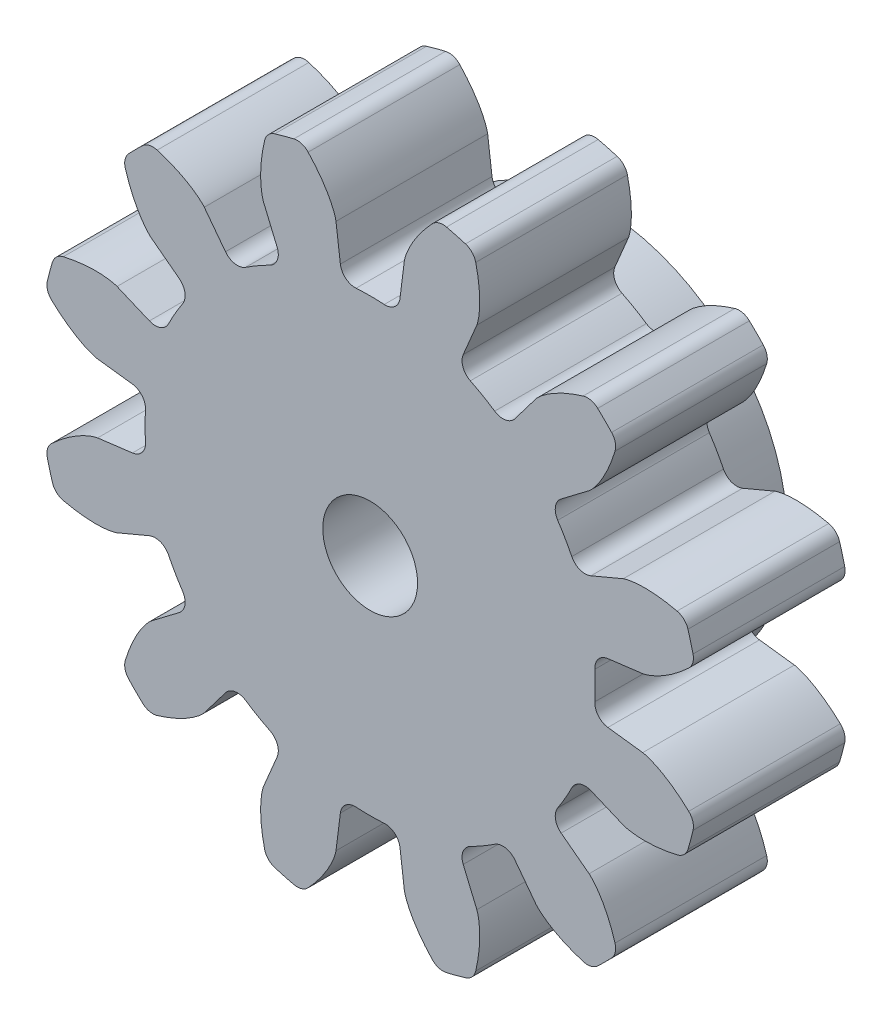
SolidWorks part; units mm, degrees
material "Brass"
ref_plane "Front Plane" through (0, 0, 0) normal (0, 0, 1) x (1, 0, 0)
ref_plane "Top Plane" through (0, 0, 0) normal (0, 1, 0) x (1, 0, 0)
ref_plane "Right Plane" through (0, 0, 0) normal (1, 0, 0) x (0, 0, -1)
sketch "Sketch1" plane through (0, 0, 0) normal (0, 0, 1) x (1, 0, 0)
  circle A0 centre (0, 0) radius 8.75
  dimension "D1" = 17.5
extrude "Boss-Extrude1" add sketch "Sketch1" along normal blind 4
sketch "Sketch2" plane through (0, 0, 4) normal (0, 0, 1) x (1, 0, 0)
  line L0 (7.1881, 0.9014) -> (0, 0) construction
  line L1 (0, 0) -> (7.1881, -0.9014) construction
  line L2 (5.8914, 0.7388) -> (7.1881, 0.9014)
  line L3 (5.8914, -0.7388) -> (7.1881, -0.9014)
  circle A0 centre (0, 0) radius 8.75 construction
  circle A1 centre (0, 0) radius 7.2444 construction
  circle A2 centre (0, 0) radius 7.5 construction
  circle A3 centre (0, 0) radius 5.9375 construction
  arc A4 (8.5637, 1.7962) -> (8.5637, -1.7962) centre (3.6281, 0) cw
  arc A5 (5.8914, -0.7388) -> (5.8914, 0.7388) centre (0, 0) ccw
  spline S0 degree 4 poles (7.1881, 0.9014) (7.1906, 0.9017) (7.1974, 0.9028) (7.2102, 0.9052) (7.231, 0.9098) (7.2574, 0.9165) (7.2912, 0.9262) (7.3308, 0.939) (7.374, 0.9543) (7.4206, 0.9724) (7.4667, 0.9918) (7.5124, 1.0122) (7.5575, 1.0337) (7.6118, 1.061) (7.6764, 1.0954) (7.7509, 1.1381) (7.8343, 1.1894) (7.9181, 1.2449) (7.9996, 1.302) (8.0806, 1.3625) (8.158, 1.4231) (8.2371, 1.489) (8.3094, 1.5512) (8.3888, 1.6241) (8.4524, 1.6838) (8.5346, 1.7659) (8.5825, 1.8154) (8.6381, 1.8744) (8.6624, 1.9012) (8.6774, 1.9177) knots 0 0 0 0 0 0.005377 0.015084 0.028532 0.04661 0.064855 0.092111 0.119476 0.146842 0.174209 0.201575 0.228941 0.256307 0.307035 0.361767 0.4165 0.471232 0.525964 0.580697 0.635429 0.690161 0.744894 0.799626 0.854358 0.909091 0.954545 1 1 1 1 1 construction
  spline S1 degree 4 poles (7.1881, 0.9014) (7.1906, 0.9017) (7.1974, 0.9028) (7.2102, 0.9052) (7.231, 0.9098) (7.2574, 0.9165) (7.2912, 0.9262) (7.3308, 0.939) (7.374, 0.9543) (7.4206, 0.9724) (7.4667, 0.9918) (7.5124, 1.0122) (7.5575, 1.0337) (7.6118, 1.061) (7.6764, 1.0954) (7.7509, 1.1381) (7.8343, 1.1894) (7.9181, 1.2449) (7.9996, 1.302) (8.0806, 1.3625) (8.158, 1.4231) (8.2371, 1.489) (8.3094, 1.5512) (8.3888, 1.6241) (8.4524, 1.6838) (8.5167, 1.7481) (8.5479, 1.7798) (8.5637, 1.7962) knots 0 0 0 0 0 0.005377 0.015084 0.028532 0.04661 0.064855 0.092111 0.119476 0.146842 0.174209 0.201575 0.228941 0.256307 0.307035 0.361767 0.4165 0.471232 0.525964 0.580697 0.635429 0.690161 0.744894 0.799626 0.854358 0.909091 0.909091 0.909091 0.909091 0.909091
  spline S2 degree 4 poles (7.1881, -0.9014) (7.1906, -0.9017) (7.1974, -0.9028) (7.2102, -0.9052) (7.231, -0.9098) (7.2574, -0.9165) (7.2912, -0.9262) (7.3308, -0.939) (7.374, -0.9543) (7.4206, -0.9724) (7.4667, -0.9918) (7.5124, -1.0122) (7.5575, -1.0337) (7.6118, -1.061) (7.6764, -1.0954) (7.7509, -1.1381) (7.8343, -1.1894) (7.9181, -1.2449) (7.9996, -1.302) (8.0806, -1.3625) (8.158, -1.4231) (8.2371, -1.489) (8.3094, -1.5512) (8.3888, -1.6241) (8.4524, -1.6838) (8.5346, -1.7659) (8.5825, -1.8154) (8.6381, -1.8744) (8.6624, -1.9012) (8.6774, -1.9177) knots 0 0 0 0 0 0.005377 0.015084 0.028532 0.04661 0.064855 0.092111 0.119476 0.146842 0.174209 0.201575 0.228941 0.256307 0.307035 0.361767 0.4165 0.471232 0.525964 0.580697 0.635429 0.690161 0.744894 0.799626 0.854358 0.909091 0.954545 1 1 1 1 1 construction
  spline S3 degree 4 poles (7.1881, -0.9014) (7.1906, -0.9017) (7.1974, -0.9028) (7.2102, -0.9052) (7.231, -0.9098) (7.2574, -0.9165) (7.2912, -0.9262) (7.3308, -0.939) (7.374, -0.9543) (7.4206, -0.9724) (7.4667, -0.9918) (7.5124, -1.0122) (7.5575, -1.0337) (7.6118, -1.061) (7.6764, -1.0954) (7.7509, -1.1381) (7.8343, -1.1894) (7.9181, -1.2449) (7.9996, -1.302) (8.0806, -1.3625) (8.158, -1.4231) (8.2371, -1.489) (8.3094, -1.5512) (8.3888, -1.6241) (8.4524, -1.6838) (8.5167, -1.7481) (8.5479, -1.7798) (8.5637, -1.7962) knots 0 0 0 0 0 0.005377 0.015084 0.028532 0.04661 0.064855 0.092111 0.119476 0.146842 0.174209 0.201575 0.228941 0.256307 0.307035 0.361767 0.4165 0.471232 0.525964 0.580697 0.635429 0.690161 0.744894 0.799626 0.854358 0.909091 0.909091 0.909091 0.909091 0.909091
  circle M4 centre (0, 0) radius 8.75
  dimension "D1" = 17.5
  dimension "D2" = 11.875
  dimension "D3" = 15
  dimension "D4" = 14.4889
extrude "Cut-Extrude1" cut sketch "Sketch2" against normal through all contours L3 S3 S1 L2 A5 M4 region at (7.5286, 0, 4)
sketch "Mate" plane through (0, 0, 0) normal (0, 0, 1) x (1, 0, 0)
  circle A0 centre (0, 0) radius 7.5
  circle A1 centre (0, 0) radius 7.5 construction
fillet "Fillet1" radius 0.3934 4 edges at (5.8914, -0.7388, 2) (5.8914, 0.7388, 2) (8.5637, -1.7962, 2) (8.5637, 1.7962, 2)
pattern_circular "CirPattern1" count 12 over 360 about axis through (0, 0, 0) along (0, 0, 1) of "Cut-Extrude1", "Fillet1"
sketch "Sketch4" plane through (0, 0, 0) normal (0, 0, 1) x (1, 0, 0)
  circle A0 centre (0, 0) radius 5
  dimension "D1" = 10
extrude "Boss-Extrude2" add sketch "Sketch4" against normal blind 2
sketch "Sketch3" plane through (0, 0, 0) normal (0, 0, 1) x (1, 0, 0)
  circle A0 centre (0, 0) radius 2.9
  dimension "D1" = 5.8
extrude "Cut-Extrude2" cut sketch "Sketch3" along normal blind 2 and the other way blind 2
sketch "Sketch5" plane through (0, 0, 0) normal (0, 0, 1) x (1, 0, 0)
  circle A0 centre (0, 0) radius 1.25
  dimension "D1" = 2.5
extrude "Cut-Extrude3" cut sketch "Sketch5" along normal through all
equation "\"DiametralPitch\"= 0.8"
equation "\"NumTeeth\"= 12"
equation "\"Addendum\"= 1 / \"DiametralPitch\""
equation "\"Dedendum\"= 1.25 / \"DiametralPitch\""
equation "\"WorkingDepth\"= 2 / \"DiametralPitch\""
equation "\"WholeDepth\"= 2.25 / \"DiametralPitch\""
equation "\"Clearance\"= 0.25 / \"DiametralPitch\""
equation "\"ToothThickness\"= 1.5708 / \"DiametralPitch\""
equation "\"CircularPitch\"= pi / \"DiametralPitch\""
equation "\"PitchCircle\"= \"NumTeeth\" / \"DiametralPitch\""
equation "\"OutsideDiameter\"= ( \"NumTeeth\" + 2 ) / \"DiametralPitch\""
equation "\"AddendumCircle\"= \"PitchCircle\" + ( 2 * \"Addendum\" )"
equation "\"DedendumCircle\"= \"PitchCircle\" - ( 2 * \"Dedendum\" )"
equation "\"PitchAngle\"= 360deg / \"NumTeeth\""
equation "\"PressureAngle\"= 15deg"
equation "\"Width\"= 4mm"
equation "\"Fillet\"= \"Clearance\" * cos ( \"PressureAngle\" ) * tan ( ( 90 + \"PressureAngle\" ) / 2 )"
equation "\"BaseCircle\"= \"PitchCircle\" * cos ( \"PressureAngle\" )"
equation "\"Alpha\"= sqr ( \"PitchCircle\" ^ 2 - \"BaseCircle\" ^ 2 ) / \"BaseCircle\" * 180 / PI - \"PressureAngle\""
equation "\"Beta\"= ( \"PitchAngle\" / 4 - \"Alpha\" )"
equation "\"Phi\"= sqr ( ( \"AddendumCircle\" / 2 ) ^ 2 - ( \"BaseCircle\" / 2 ) ^ 2 ) / ( \"BaseCircle\" / 2 )"
equation "\"D1@Sketch1\"=\"OutsideDiameter\""
equation "\"D1@Boss-Extrude1\"=\"Width\""
equation "\"D1@Sketch2\"=\"OutsideDiameter\""
equation "\"D2@Sketch2\"=\"DedendumCircle\""
equation "\"D3@Sketch2\"=\"PitchCircle\""
equation "\"D4@Sketch2\"=\"BaseCircle\""
equation "\"D1@Fillet1\"=\"Fillet\""
equation "\"D1@CirPattern1\"=\"NumTeeth\""
